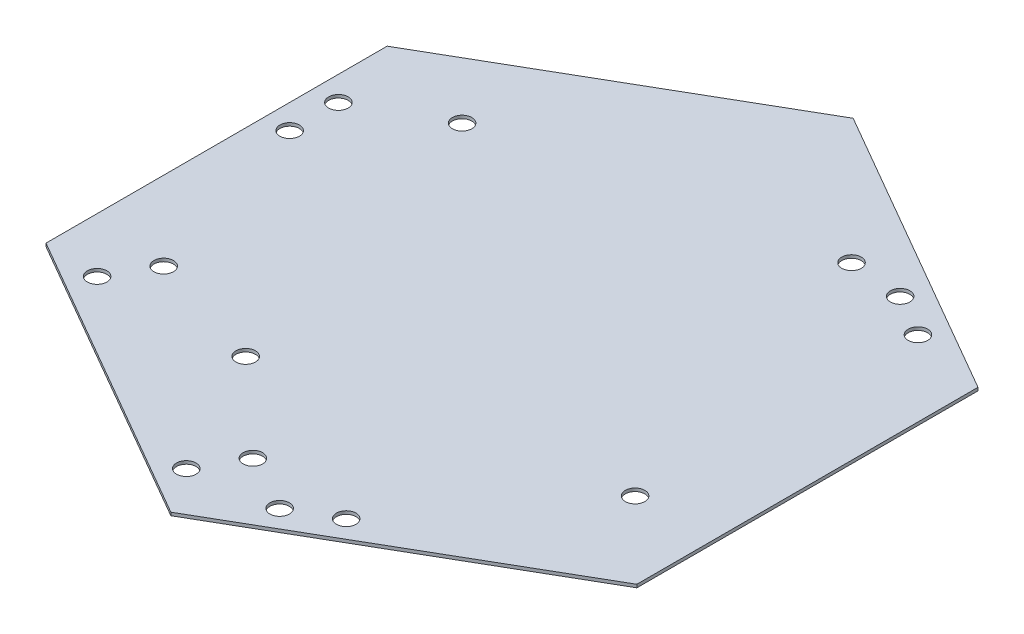
SolidWorks part; units mm, degrees
material "5052-H32"
ref_plane "Front Plane" through (0, 0, 0) normal (0, 0, 1) x (1, 0, 0)
ref_plane "Top Plane" through (0, 0, 0) normal (0, 1, 0) x (1, 0, 0)
ref_plane "Right Plane" through (0, 0, 0) normal (1, 0, 0) x (0, 0, -1)
sketch "Sketch1" plane through (0, 0, 0) normal (0, 1, 0) x (1, 0, 0)
  line L0 (13.3228, -73.8757) -> (24.3213, -67.5257) construction
  line L1 (0, 88.9) -> (-76.9897, 44.45)
  line L2 (-76.9897, 44.45) -> (-76.9897, -44.45)
  line L3 (-76.9897, -44.45) -> (0, -88.9)
  line L4 (0, -88.9) -> (76.9897, -44.45)
  line L5 (76.9897, -44.45) -> (76.9897, 44.45)
  line L6 (76.9897, 44.45) -> (0, 88.9)
  line L7 (24.3213, -67.5257) -> (27.4963, -73.025) construction
  line L8 (-70.6397, 12.7) -> (-76.9897, 12.7) construction
  line L9 (-70.6397, 25.4) -> (-70.6397, 12.7) construction
  line L10 (46.3184, 54.8257) -> (49.4934, 60.325) construction
  line L11 (57.3169, 48.4757) -> (46.3184, 54.8257) construction
  circle A0 centre (0, 0) radius 76.9897 construction
  circle A1 centre (13.3228, -73.8757) radius 2.54
  circle A2 centre (24.3213, -67.5257) radius 2.54
  circle A7 centre (-70.6397, 12.7) radius 2.54
  circle A8 centre (-70.6397, 25.4) radius 2.54
  circle A9 centre (46.3184, 54.8257) radius 2.54
  circle A10 centre (57.3169, 48.4757) radius 2.54
  point P13 (38.4948, -66.675)
  point P28 (3.175, -1.8331)
  point P29 (0, 0)
  dimension "D2" = 5.08
  dimension "D3" = 6.35
  dimension "D4" = 12.7
  dimension "D1" = 177.8
  dimension "D5" = 12.7
  dimension "D6" = 3
extrude "Boss-Extrude1" add sketch "Sketch1" along normal blind 0.8128
sketch "Sketch2" plane through (0, 0.8128, 0) normal (0, 1, 0) x (1, 0, 0)
  line L0 (-49.8503, 36.8467) -> (56.8353, -24.7483) construction
  line L1 (27.9428, -74.7916) -> (-78.7428, -13.1966) construction
  line L2 (27.9428, -74.7916) -> (85.7278, 25.295) construction
  line L3 (85.7278, 25.295) -> (-20.9578, 86.89) construction
  line L4 (-78.7428, -13.1966) -> (-20.9578, 86.89) construction
  line L5 (-76.9897, -44.45) -> (0, -88.9) construction
  line L6 (32.385, 56.0925) -> (-25.4, -43.9941) construction
  circle A0 centre (-49.8503, 36.8467) radius 2.54
  circle A1 centre (-25.4, -43.9941) radius 2.54
  circle A2 centre (32.385, 56.0925) radius 2.54
  circle A3 centre (56.8353, -24.7483) radius 2.54
  dimension "D5" = 5.08
  dimension "D6" = 57.785
  dimension "D1" = 123.19
  dimension "D2" = 115.57
  dimension "D3" = 61.595
  dimension "D4" = 50.8
  dimension "D7" = 61.595
extrude "Cut-Extrude1" cut sketch "Sketch2" against normal through all
sketch "Sketch3" plane through (0, 0.8128, 0) normal (0, 1, 0) x (1, 0, 0)
  line L0 (-62.8161, -45.3007) -> (-65.9911, -50.8) construction
  line L2 (-76.9897, -44.45) -> (0, -88.9) construction
  line L3 (-62.8161, -45.3007) -> (-7.8235, -77.0507) construction
  line L4 (-35.3198, -61.1757) -> (-38.4948, -66.675) construction
  line L5 (-56.4661, -34.3022) -> (-62.8161, -45.3007) construction
  line L6 (-56.4661, -34.3022) -> (-1.4735, -66.0522) construction
  circle A1 centre (-7.8235, -77.0507) radius 2.54
  circle A2 centre (-62.8161, -45.3007) radius 2.54
  circle A3 centre (-56.4661, -34.3022) radius 2.54
  circle A4 centre (-1.4735, -66.0522) radius 2.54
  dimension "D1" = 5.08
  dimension "D2" = 6.35
  dimension "D3" = 63.5
  dimension "D4" = 12.7
extrude "Cut-Extrude2" cut sketch "Sketch3" against normal through all
